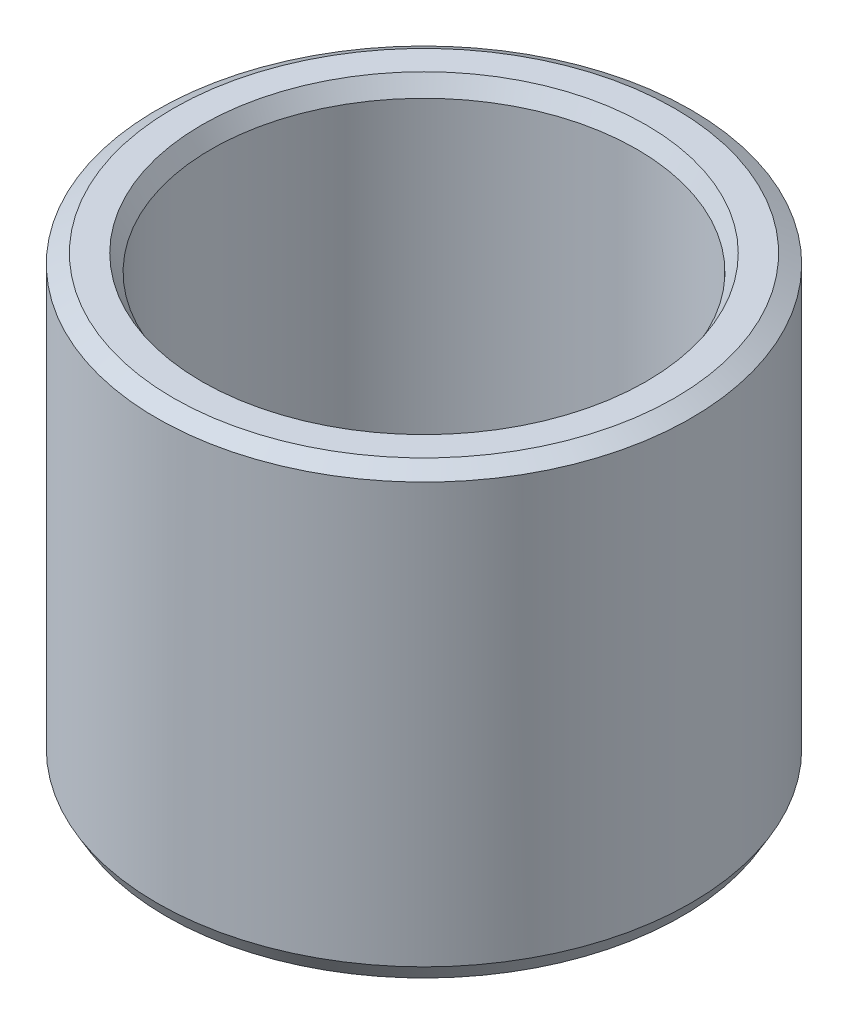
SolidWorks part; units mm, degrees
ref_plane "Front Plane" through (0, 0, 0) normal (0, 0, 1) x (1, 0, 0)
ref_plane "Top Plane" through (0, 0, 0) normal (0, 1, 0) x (1, 0, 0)
ref_plane "Right Plane" through (0, 0, 0) normal (1, 0, 0) x (0, 0, -1)
sketch "Sketch1" plane through (0, 0, 0) normal (0, 1, 0) x (1, 0, 0)
  circle A0 centre (0, 0) radius 50
  dimension "SLEEVE_OD" = 100
extrude "Boss-Extrude1" add sketch "Sketch1" along normal blind 83.4086
sketch "Sketch2" plane through (0, 0, 0) normal (0, 1, 0) x (1, 0, 0)
  circle A0 centre (0, 0) radius 39.8411
  dimension "BORE_D" = 79.6822
extrude "Cut-Extrude1" cut sketch "Sketch2" along normal through all
chamfer "Chamfer1" distance 1.7629 angle 60 4 edges at (0, 83.4086, 39.8411) (0, 0, 39.8411) (0, 0, 50) (0, 83.4086, 50) first distance on face at (0, 83.4086, 39.8411) first distance on face at (0, 0, 39.8411) first distance on face at (0, 83.4086, 50)
